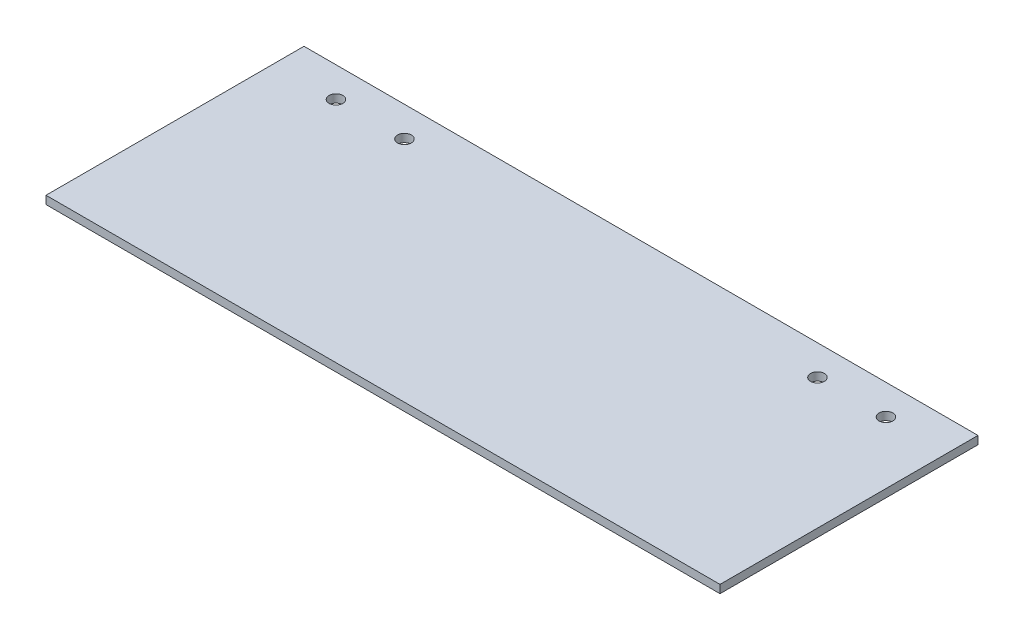
SolidWorks part; units mm, degrees
ref_plane "Front Plane" through (0, 0, 0) normal (0, 0, 1) x (1, 0, 0)
ref_plane "Top Plane" through (0, 0, 0) normal (0, 1, 0) x (1, 0, 0)
ref_plane "Right Plane" through (0, 0, 0) normal (1, 0, 0) x (0, 0, -1)
sketch "Sketch1" plane through (0, 0, 0) normal (0, 1, 0) x (1, 0, 0)
  line L0 (125, 95.7) -> (125, 0) construction
  line L1 (0, 95.7) -> (250, 95.7)
  line L2 (0, 95.7) -> (0, 0)
  line L3 (0, 0) -> (250, 0)
  line L4 (250, 95.7) -> (250, 0)
  circle A0 centre (23, 84.56) radius 2.564
  circle A1 centre (48.4, 84.56) radius 2.564
  circle A2 centre (201.6, 84.56) radius 2.564
  circle A3 centre (227, 84.56) radius 2.564
  dimension "D2" = 5.128
  dimension "D1" = 250
  dimension "D3" = 25.4
  dimension "D4" = 23
  dimension "D5" = 11.14
  dimension "D6" = 84.56
extrude "Boss-Extrude1" add sketch "Sketch1" along normal blind 3
equation "\"cf_tube_outer_diameter\"= 25mm"
equation "\"cf_tube_inner_diameter\"= 21mm"
equation "\"mid_plate_mid_to_top\"= 100mm"
equation "\"mid_plate_mid_to_bottom\"= 30mm"
equation "\"mid_plate_horizontal_spacing\"= 250mm"
equation "\"cf_plate_thickness\"= 3mm"
equation "\"mid_tube_length\"= 500mm"
equation "\"mid_plate_bottom_width\"= 180mm"
equation "\"mid_support_plate_distance\"= 250mm"
equation "\"nut_strip_2_hole_distance\"= 7mm"
equation "\"nut_strip_hole_diameter\"= 2.5mm"
equation "\"nut_strip_hole_to_edge_distance\"= 2.5mm"
